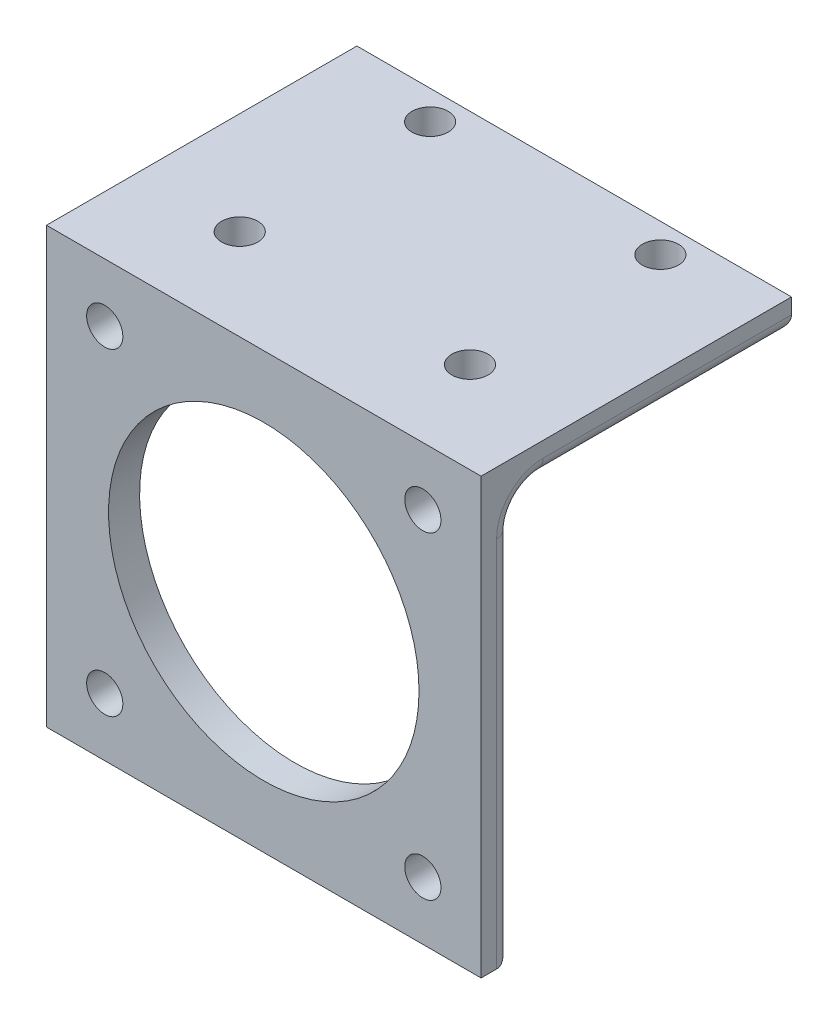
SolidWorks part; units mm, degrees
ref_plane "Plan de face" through (0, 0, 0) normal (0, 0, 1) x (1, 0, 0)
ref_plane "Plan de dessus" through (0, 0, 0) normal (0, 1, 0) x (1, 0, 0)
ref_plane "Plan de droite" through (0, 0, 0) normal (1, 0, 0) x (0, 0, -1)
sketch "Esquisse1" plane through (0, 0, 0) normal (0, 0, 1) x (1, 0, 0)
  line L1 (-42, 42) -> (0, 42)
  line L2 (-42, 42) -> (-42, 0)
  line L3 (-42, 0) -> (0, 0)
  line L4 (0, 42) -> (0, 0)
  dimension "D1" = 42
  dimension "D2" = 42
extrude "Boss.-Extru.1" add sketch "Esquisse1" along normal blind 3
sketch "Esquisse2" plane through (0, 0, 3) normal (0, 0, 1) x (1, 0, 0)
  line L0 (-21, 42) -> (-21, -2.4275) construction
  line L1 (0, 42) -> (-5.63, 42)
  line L2 (0, 42) -> (0, 36.37)
  line L3 (0, 36.37) -> (-5.63, 36.37) construction
  line L4 (-5.63, 42) -> (-5.63, 36.37) construction
  line L5 (0, 42) -> (-42, 42) construction
  line L6 (-42, 21) -> (0, 21) construction
  line L7 (-42, 42) -> (-42, 0) construction
  line L8 (0, 0) -> (0, 42) construction
  circle A0 centre (-5.63, 36.37) radius 1.75
  circle A1 centre (-36.37, 36.37) radius 1.75
  circle A2 centre (-5.63, 5.63) radius 1.75
  circle A3 centre (-36.37, 5.63) radius 1.75
  circle A4 centre (-21, 21) radius 15
  dimension "D3" = 3.5
  dimension "D4" = 30
  dimension "D1" = 5.63
  dimension "D2" = 5.63
extrude "Enlèv. mat.-Extru.1" cut sketch "Esquisse2" against normal blind 3 contours A4 | A1 | A3 | A2 | A0
sketch "Esquisse5" plane through (0, 42, 0) normal (0, 1, 0) x (1, 0, 0)
  line L1 (-42, -3) -> (0, -3)
  line L2 (-42, -3) -> (-42, 27)
  line L3 (-42, 27) -> (0, 27)
  line L4 (0, -3) -> (0, 27)
  dimension "D1" = 30
extrude "Boss.-Extru.2" add sketch "Esquisse5" against normal blind 3
fillet "Congé1" radius 3 1 edges at (-21, 39, 0)
sketch "Esquisse6" plane through (0, 0, 0) normal (0, 0, -1) x (-1, 0, 0)
  line L0 (21, 36) -> (21, 0) construction
  circle A0 centre (36.37, 36.37) radius 3
  circle A1 centre (5.63, 36.37) radius 3
  dimension "D1" = 6
extrude "Enlèv. mat.-Extru.2" cut sketch "Esquisse6" along normal through all contours A0 | A1
sketch "Esquisse7" plane through (0, 39, 0) normal (0, -1, 0) x (1, 0, 0)
  line L2 (-42, -15) -> (0, -15) construction
  line L3 (-28.5, -7.5) -> (-13.5, -7.5)
  line L4 (-28.5, -7.5) -> (-28.5, -22.5)
  line L5 (-28.5, -22.5) -> (-13.5, -22.5)
  line L6 (-13.5, -7.5) -> (-13.5, -22.5)
  line L7 (-42, -27) -> (-42, -3) construction
  line L8 (0, -3) -> (0, -27) construction
  line L9 (-21, -3) -> (-21, -27) construction
  line L10 (-7.0733, -3) -> (-34.9267, -3) construction
  line L11 (-7.0733, -27) -> (-34.9267, -27) construction
  line L12 (-34.9267, -3) -> (-34.9267, -27) construction
  circle A0 centre (-32.1267, -5.8) radius 1.75
  circle A1 centre (-9.8733, -5.8) radius 1.75
  circle A2 centre (-9.8733, -24.2) radius 1.75
  circle A3 centre (-32.1267, -24.2) radius 1.75
  dimension "D5" = 3.5
  dimension "D6" = 2.8
  dimension "D1" = 15
  dimension "D2" = 15
  dimension "D3" = 7.5
  dimension "D4" = 7.5
  dimension "D7" = 2.8
extrude "Enlèv. mat.-Extru.3" cut sketch "Esquisse7" against normal blind 3 contours A0 | A1 | A3 | A2
fillet "Congé2" radius 1.5 8 edges at (-42, 38.1213, -0.8787) (-42, 39, -15) (-2.0934, 39, -27) (0, 39, -15) (0, 38.1213, -0.8787) (-21, 0, 0) (-42, 18, 0) (0, 18, 0)
